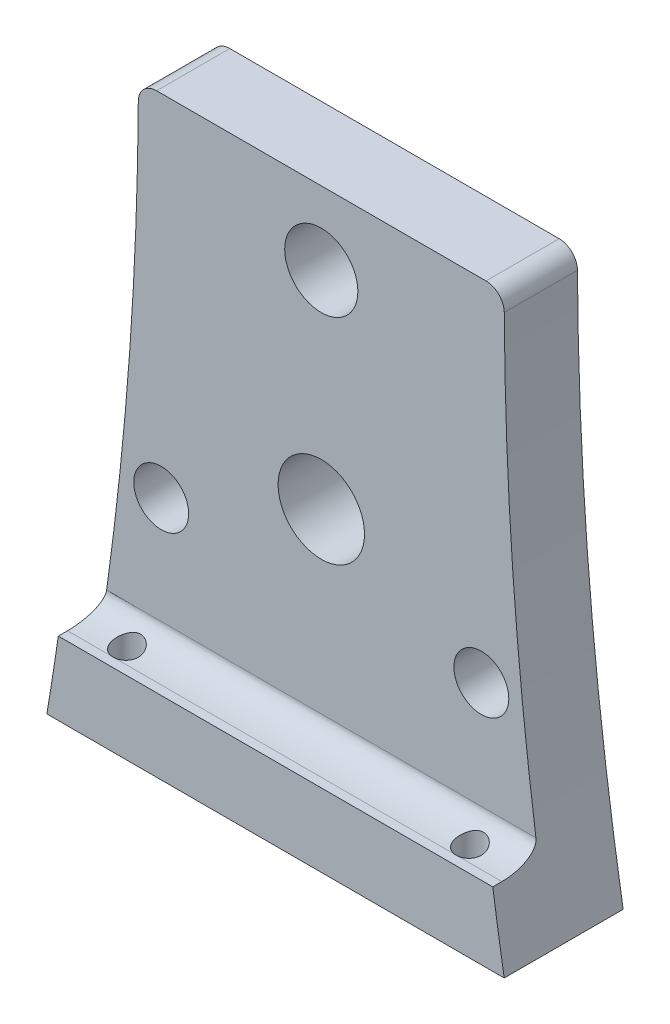
SolidWorks part; units mm, degrees
ref_plane "Front Plane" through (0, 0, 0) normal (0, 0, 1) x (1, 0, 0)
ref_plane "Top Plane" through (0, 0, 0) normal (0, 1, 0) x (1, 0, 0)
ref_plane "Right Plane" through (0, 0, 0) normal (1, 0, 0) x (0, 0, -1)
sketch "Sketch1" plane through (0, 0, 0) normal (0, 0, 1) x (1, 0, 0)
  line L0 (-20, 60) -> (-20, 0) construction
  line L3 (20, 60) -> (-20, 60)
  line L5 (25, 0) -> (-25, 0)
  line L6 (0, 60) -> (0, 0) construction
  arc A0 (-25, 0) -> (-20, 60) centre (-382.5, 60) ccw
  arc A1 (25, 0) -> (20, 60) centre (382.5, 60) cw
  dimension "D1" = 60
  dimension "D2" = 25
  dimension "D3" = 20
extrude "Boss-Extrude1" add sketch "Sketch1" along normal blind 8
sketch "Sketch2" plane through (0, 0, 8) normal (0, 0, 1) x (1, 0, 0)
  line L0 (-25, 0) -> (25, 0) construction
  line L1 (-25, 0) -> (25, 0)
  line L2 (-23.749, 8) -> (23.749, 8)
  arc A0 (20, 60) -> (25, 0) centre (382.5, 60) ccw construction
  arc A1 (-25, 0) -> (-20, 60) centre (-382.5, 60) ccw construction
  arc A2 (23.749, 8) -> (25, 0) centre (382.5, 60) ccw
  arc A3 (-25, 0) -> (-23.749, 8) centre (-382.5, 60) ccw
  dimension "D1" = 8
extrude "Boss-Extrude2" add sketch "Sketch2" along normal blind 5
sketch "Sketch3" plane through (0, 8, 0) normal (0, 1, 0) x (1, 0, 0)
  line L0 (-23.749, -10.5) -> (23.749, -10.5) construction
  line L1 (-23.749, -13) -> (-23.749, -8) construction
  line L2 (23.749, -13) -> (23.749, -8) construction
  line L3 (0, 0) -> (0, -13) construction
  line L4 (23.749, -13) -> (-23.749, -13) construction
  circle A0 centre (-18.749, -10.5) radius 1.5
  circle A1 centre (18.749, -10.5) radius 1.5
  dimension "D1" = 3
  dimension "D2" = 5
extrude "Cut-Extrude" cut sketch "Sketch3" against normal up to surface (8 mm away) up to face at (0, 0, 6.5)
fillet "Fillet1" radius 2 1 edges at (0, 8, 8) second distance 4 first distance on face at (0, 33.9663, 8)
fillet "Fillet2" radius 2 2 edges at (20, 60, 4) (-20, 60, 4)
sketch "Sketch4" plane through (0, 0, 0) normal (0, 0, -1) x (-1, 0, 0)
  line L0 (-18.0055, 60) -> (18.0055, 60) construction
  line L1 (-4.725, 29.37) -> (4.725, 29.37) construction
  line L2 (0, 35.695) -> (0, 7.695) construction
  line L3 (0, 34.095) -> (0, 24.645) construction
  line L4 (-20.5, 21.695) -> (-14.5, 21.695) construction
  circle A0 centre (0, 52) radius 4.0005
  circle A1 centre (0, 29.37) radius 4.725
  circle A2 centre (-17.5, 21.695) radius 3
  circle A3 centre (0, 21.695) radius 14 construction
  circle A4 centre (17.5, 21.695) radius 3
  dimension "D1" = 8.001
  dimension "D3" = 9.45
  dimension "D5" = 6
  dimension "D7" = 28
  dimension "D2" = 8
  dimension "D4" = 22.63
  dimension "D6" = 20.5
  dimension "D8" = 1.6
extrude "M4*H6 T-Insert" cut sketch "Sketch4" against normal up to surface (8 mm away) up to face at (-3.3342, 42.8079, 8)
sketch "Sketch7" [suppressed] plane through (0, 0, 7) normal (0, 0, 1) x (1, 0, 0)
  line L0 (-13.3326, 40) -> (13.3326, 40)
  line L2 (11.0033, 60) -> (-11.0033, 60)
  line L3 (-15.0817, 10) -> (15.0817, 10)
  line L4 (11.0033, 60) -> (-11.0033, 60)
  arc A0 (-15.0817, 10) -> (-13.0033, 58.0066) centre (-614.5, 60) ccw construction
  arc A1 (13.0033, 58.0066) -> (15.0817, 10) centre (614.5, 60) ccw construction
  arc A4 (13.0033, 58.0066) -> (15.0817, 10) centre (614.5, 60) ccw
  arc A5 (13.0033, 58.0066) -> (11.0033, 60) centre (11.0033, 58) ccw
  arc A6 (-11.0033, 60) -> (-13.0033, 58.0066) centre (-11.0033, 58) ccw
  arc A7 (-15.0817, 10) -> (-13.0033, 58.0066) centre (-614.5, 60) ccw
  arc A8 (13.0033, 58.0066) -> (13.3326, 40) centre (614.5, 60) ccw
  arc A9 (13.0033, 58.0066) -> (11.0033, 60) centre (11.0033, 58) ccw
  arc A10 (-11.0033, 60) -> (-13.0033, 58.0066) centre (-11.0033, 58) ccw
  arc A11 (-13.3326, 40) -> (-13.0033, 58.0066) centre (-614.5, 60) ccw
  dimension "D2" = 20
  dimension "D1" = 0
sketch "Sketch8" plane through (0, 0, 0) normal (0, 0, -1) x (-1, 0, 0)
  line L0 (-18.0055, 60) -> (18.0055, 60) construction
  line L1 (22.5594, 17) -> (-22.5594, 17)
  line L2 (22.5594, 17) -> (22.5594, 57)
  line L3 (22.5594, 57) -> (-22.5594, 57)
  line L4 (-22.5594, 17) -> (-22.5594, 57)
  line L5 (25, 0) -> (-25, 0) construction
  arc A0 (20.0055, 58.011) -> (25, 0) centre (382.5, 60) ccw construction
  arc A1 (-25, 0) -> (-20.0055, 58.011) centre (-382.5, 60) ccw construction
  dimension "D1" = 3
  dimension "D2" = 17
extrude "Short Cut 1" [suppressed] cut sketch "Sketch8" against normal blind 10 flip side to cut
sketch "Sketch9" [suppressed] plane through (0, 0, 0) normal (1, 0, 0) x (0, 0, -1)
  line L0 (-8, 57) -> (0, 57) construction
  line L1 (0, 17) -> (-5.5, 17)
  line L2 (0, 17) -> (0, 57)
  line L3 (0, 57) -> (-5.5, 57)
  line L4 (-5.5, 17) -> (-5.5, 57)
  dimension "D1" = 5.5
extrude "Short Cut 2" [suppressed] cut sketch "Sketch9" against normal through all both and the other way through all
sketch "Sketch10" plane through (0, 0, 0) normal (0, 0, -1) x (-1, 0, 0)
  line L1 (25, 2) -> (-25, 2)
  line L2 (25, 2) -> (25, 62)
  line L3 (25, 62) -> (-25, 62)
  line L4 (-25, 2) -> (-25, 62)
  point P6 (0, 2)
  dimension "D1" = 2
  dimension "D2" = 50
  dimension "D3" = 60
extrude "Short Cut 3" [suppressed] cut sketch "Sketch10" against normal through all
